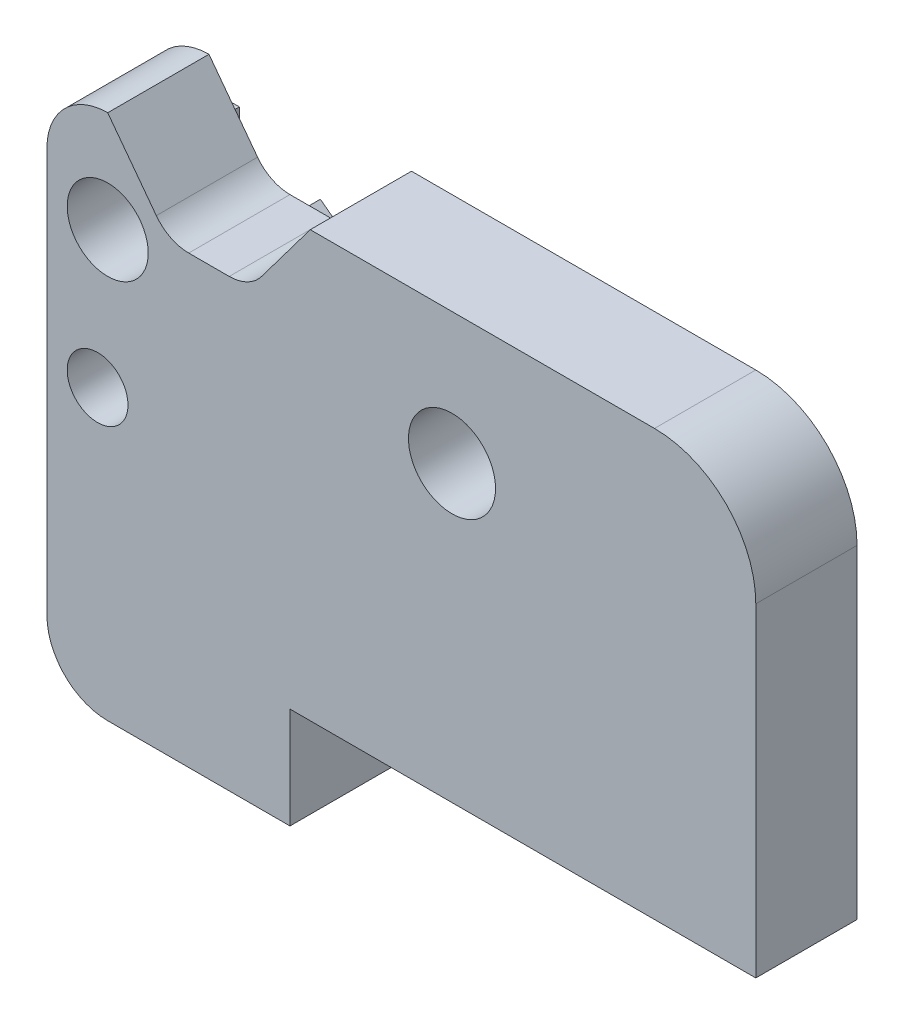
SolidWorks part; units mm, degrees
ref_plane "Front" through (0, 0, 0) normal (0, 0, 1) x (1, 0, 0)
ref_plane "Top" through (0, 0, 0) normal (0, 1, 0) x (1, 0, 0)
ref_plane "Right" through (0, 0, 0) normal (1, 0, 0) x (0, 0, -1)
sketch "Sketch1" plane through (0, 0, 0) normal (0, 0, 1) x (1, 0, 0)
  line L0 (-8, 6.5) -> (-8, -14.5)
  line L1 (-8, -14.5) -> (15, -14.5)
  line L2 (15, -14.5) -> (15, 6.5)
  line L3 (15, 6.5) -> (-8, 6.5)
  dimension "D1" = 8
  dimension "D2" = 15
  dimension "D3" = 6.5
  dimension "D4" = 14.5
extrude "Extrude1" add sketch "Sketch1" along normal blind 5
sketch "Sketch2" plane through (0, 0, 5) normal (0, 0, 1) x (1, 0, 0)
  circle A0 centre (0, 0) radius 2.15
  dimension "D1" = 4.3
extrude "Extrude2" cut sketch "Sketch2" against normal blind 4.5
sketch "Sketch4" plane through (0, -14.5, 0) normal (0, -1, 0) x (1, 0, 0)
  line L0 (-8, 0) -> (15, 0) construction
  line L1 (-8, 5) -> (-8, 0) construction
  line L2 (15, 5) -> (15, 0) construction
  circle A0 centre (-1.4, 2.5) radius 1.25
  circle A1 centre (12, 2.5) radius 1.25
  dimension "D1" = 2.5
  dimension "D2" = 2.5
  dimension "D3" = 2.5
  dimension "D5" = 6.6
  dimension "D6" = 3
  dimension "D4" = 2.5
extrude "Extrude4" cut sketch "Sketch4" against normal blind 8
cosmetic thread "Hole Thread1" parameters "D1"=6, "D2"=3
cosmetic thread "Hole Thread2" parameters "D1"=6, "D2"=3
fillet "Fillet1" radius 5 1 edges at (15, 6.5, 2.5)
sketch "Sketch6" plane through (0, 0, 0) normal (0, 0, -1) x (-1, 0, 0)
  line L0 (8, -14.5) -> (-15, -14.5) construction
  line L1 (8, 6.5) -> (8, -14.5) construction
  circle A0 centre (-4.9, -6.5) radius 4.5
  dimension "D1" = 9
  dimension "D3" = 12.9
  dimension "D2" = 8
extrude "Extrude6" cut sketch "Sketch6" against normal blind 4.5
sketch "Sketch9" plane through (0, 0, 0) normal (0, 0, -1) x (-1, 0, 0)
  line L1 (8, 6.5) -> (20, 6.5)
  line L2 (8, 6.5) -> (8, -19.5)
  line L3 (8, -19.5) -> (20, -19.5)
  line L4 (20, 6.5) -> (20, -19.5)
  line L5 (8, -14.5) -> (-15, -14.5) construction
  dimension "D1" = 12
  dimension "D2" = 5
extrude "Extrude9" add sketch "Sketch9" against normal up to surface (5 mm away) up to face at (2.15, 0, 5)
sketch "Sketch10" plane through (0, 0, 5) normal (0, 0, 1) x (1, 0, 0)
  line L0 (10, 6.5) -> (-20, 6.5) construction
  line L1 (-20, -19.5) -> (-20, 6.5) construction
  circle A0 centre (-17, 1.5) radius 2
  dimension "D1" = 4
  dimension "D3" = 3
  dimension "D2" = 5
extrude "Extrude10" cut sketch "Sketch10" against normal blind 4
sketch "Sketch11" plane through (0, 0, 5) normal (0, 0, 1) x (1, 0, 0)
  line L0 (-20, -19.5) -> (-20, 6.5) construction
  line L1 (-8, -14.5) -> (15, -14.5) construction
  circle A0 centre (-17.5, -5.5) radius 1.5
  dimension "D1" = 3
  dimension "D3" = 9
  dimension "D2" = 2.5
extrude "Extrude11" cut sketch "Sketch11" against normal up to surface (5 mm away) up to face at (0.4, -6.5, 0)
hole_wizard "M3 Tapped Hole1" positions "3DSketch1" profile "Sketch12" tap size "M3" standard "DIN"
sketch3d "3DSketch1"
  line L0 (-1.4, -6.5, 2.5) -> (-1.4, -14.5, 2.5) construction
  line L1 (12, -6.5, 2.5) -> (12, -14.5, 2.5) construction
  point P0 (-1.4, -14.5, 2.5)
  point P4 (12, -14.5, 2.5)
sketch "Sketch12" plane through (-1.4, -14.5, 2.5) normal (1, 0, 0) x (0, 0, -1)
  line L0 (0, 0) -> (0, 8.7511)
  line L1 (0, 8.7511) -> (1.25, 8)
  line L2 (1.25, 8) -> (1.25, 0)
  line L5 (1.25, 0) -> (0, 0)
  line L10 (0, 8.7511) -> (-1.25, 8) construction
  line L11 (0, -6.35) -> (0, 107.95) construction
  dimension "Tap Drill Dia." = 2.5
  dimension "Tap Drill Depth" = 8
  dimension "Drill Angle" = 118
sketch "Sketch13" plane through (0, 0, 0) normal (0, 0, -1) x (-1, 0, 0)
  line L0 (20, -19.5) -> (8, -19.5)
  line L1 (20, -19.5) -> (20, 1)
  line L2 (20, 1) -> (18.1, 1)
  line L3 (20, -19.5) -> (20, 6.5) construction
  line L4 (18.1, 1) -> (2, -11.07)
  line L5 (2, -11.07) -> (2, -14.5)
  line L6 (8, -14.5) -> (-15, -14.5) construction
  line L7 (2, -14.5) -> (8, -14.5)
  line L8 (8, -14.5) -> (8, -19.5)
  dimension "D1" = 18
  dimension "D2" = 20.5
  dimension "D3" = 1.9
  dimension "D4" = 8.43
extrude "Extrude12" add sketch "Sketch13" along normal blind 4
fillet "Fillet3" radius 3 2 edges at (-20, -19.5, 0.5) (-20, 6.5, 2.5)
sketch "Sketch14" plane through (0, 0, -4) normal (0, 0, -1) x (-1, 0, 0)
  line L0 (19.5, 1) -> (19.5, -7.5)
  line L1 (20, 1) -> (18.1, 1) construction
  line L2 (19.5, -7.5) -> (15.5, -7.5)
  line L3 (15.5, -7.5) -> (15.5, -0.9492)
  line L4 (18.1, 1) -> (2, -11.07) construction
  line L5 (15.5, -0.9492) -> (18.1, 1)
  line L6 (18.1, 1) -> (19.5, 1)
  line L8 (20, -16.5) -> (20, 1) construction
  dimension "D1" = 4
  dimension "D2" = 8.5
  dimension "D3" = 0.5
extrude "Extrude14" cut sketch "Sketch14" against normal up to surface (4 mm away) up to face at (0.4, -6.5, 0)
fillet "Fillet4" radius 2 2 edges at (-19.5, -7.5, -2) (-15.5, -7.5, -2)
sketch "Sketch15" plane through (0, 0, 5) normal (0, 0, 1) x (1, 0, 0)
  line L0 (-14, 2.5) -> (-17, 6.5)
  line L1 (10, 6.5) -> (-17, 6.5) construction
  line L2 (-14, 2.5) -> (-10, 2.5)
  line L3 (-10, 2.5) -> (-7, 6.5)
  line L4 (-17, 6.5) -> (-7, 6.5)
  line L5 (-20, -16.5) -> (-20, 3.5) construction
  dimension "D1" = 6
  dimension "D2" = 4
  dimension "D3" = 10
  dimension "D4" = 4
extrude "Extrude15" cut sketch "Sketch15" against normal up to surface (5 mm away) up to face at (-8.9874, -2.9404, 0)
fillet "Fillet6" radius 2 2 edges at (-10, 2.5, 2.5) (-14, 2.5, 2.5)
